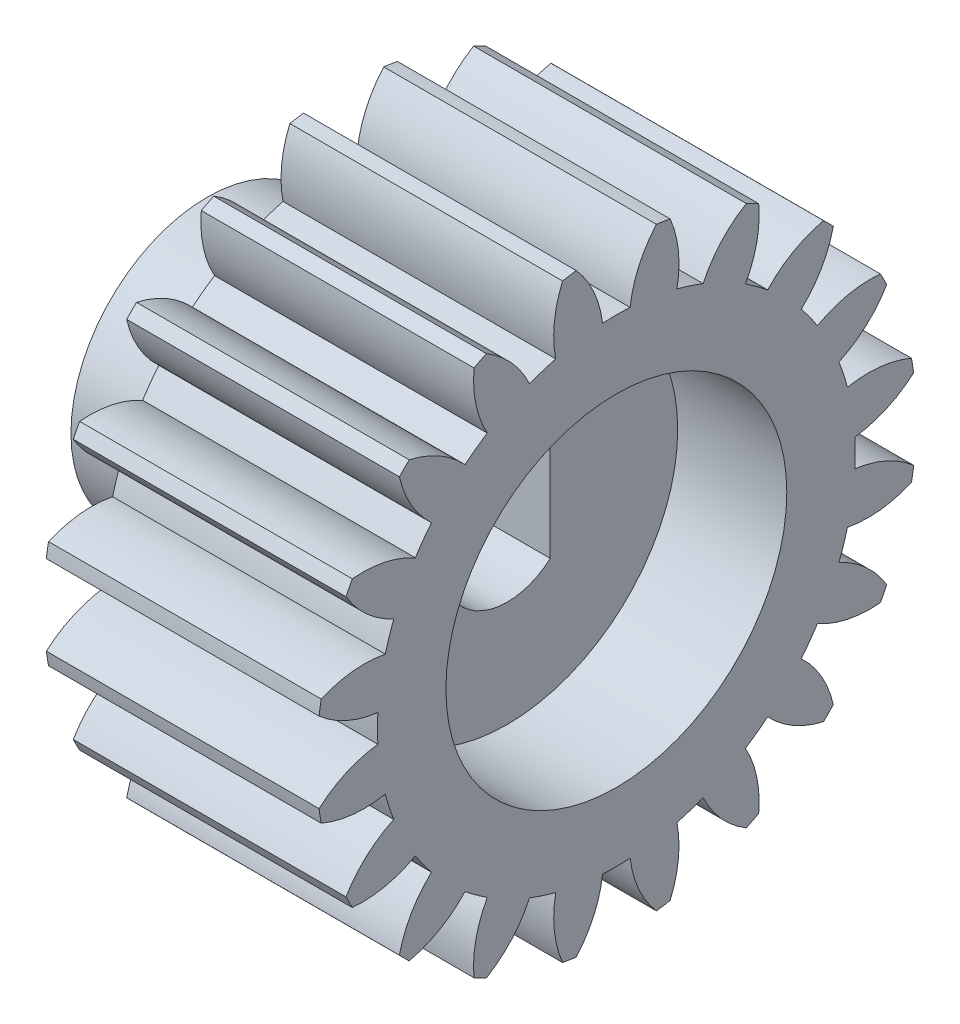
SolidWorks part; units mm, degrees
ref_plane "Plane1" through (0, 0, 0) normal (0, 0, 1) x (1, 0, 0)
ref_plane "Plane2" through (0, 0, 0) normal (0, 1, 0) x (1, 0, 0)
ref_plane "Plane3" through (0, 0, 0) normal (1, 0, 0) x (0, 0, -1)
other "Configuration Table"
sketch "HoldingSke" plane through (0, 0, 0) normal (0, 1, 0) x (1, 0, 0)
  line L0 (0, 0) -> (477.3639, -173.7462)
  line L1 (-15, 0) -> (100, 0) construction
  line L2 (0, 0) -> (-2.1039, 2.3779)
  line L3 (0, 0) -> (-11.863, 4.5341)
  line L4 (0, 0) -> (8.1152, 2.9537)
  line L5 (0, 0) -> (-17.849, -6.6571)
  line L6 (0, 0) -> (-10.5278, -7.1032)
  line L7 (-2.1039, 2.3779) -> (1.9967, 20.9815)
  line L8 (-76.2, 54.61) -> (-69.596, 54.61)
  line L9 (-71.009, 38.7566) -> (-53.1078, 45.2721)
  line L10 (-76.2, 71.12) -> (104.1128, 71.12)
  line L11 (0, 0) -> (-12.7, 0)
  line L12 (-76.2, 101.6) -> (-76.1492, 101.6)
  line L13 (24.9733, 27.94) -> (52.9518, 28.4284)
  line L14 (24.9733, 27.94) -> (25.0241, 27.9398)
  line L15 (24.9733, 27.94) -> (100.4021, 29.52)
  circle A0 centre (0, 0) radius 3.175
  circle A1 centre (0, 0) radius 6.35
  circle A2 centre (0, 0) radius 6.35
  circle A3 centre (0, 0) radius 3.175
  dimension "Num_teeth" = 20
  dimension "H" = 19.05
  dimension "Pitch_radius" = 180.3128
  dimension "Width" = 12.7
  dimension "Thickness" = 12.7
sketch "BasProSke" plane through (0, 0, 0) normal (0, 1, 0) x (1, 0, 0)
  line L0 (-10, 0) -> (60, 0) construction
  line L1 (0, 0) -> (0, 13.97)
  line L2 (0, 0) -> (12.7, 0)
  line L3 (12.7, 0) -> (12.7, 13.97)
  line L4 (12.7, 13.97) -> (0, 13.97)
  dimension "Thickness" = 12.7
  dimension "Diameter" = 27.94
revolve "Base-Revolve" add sketch "BasProSke" angle 360 about L0
sketch "TooCutSke" plane through (0, 0, 0) normal (1, 0, 0) x (0, 0, -1)
  line L1 (0, 0) -> (0, 107) construction
  line L2 (0, 0) -> (-1.0853, 12.6535) construction
  line L3 (0, 0) -> (-3.9633, 25.0231) construction
  line L4 (-1.0853, 12.6535) -> (-1.9816, 12.5116) construction
  arc A0 (0.6405, 11.1067) -> (-0.6405, 11.1067) centre (0, 0) ccw
  arc A1 (1.8856, 13.8678) -> (-1.8856, 13.8678) centre (0, 0) ccw
  circle A2 centre (0, 0) radius 12.7 construction
  circle A3 centre (0, 0) radius 11.9341 construction
  arc A4 (-0.6405, 11.1067) -> (-1.8856, 13.8678) centre (-5.6834, 10.4939) ccw
  arc A5 (1.8856, 13.8678) -> (0.6405, 11.1067) centre (5.6834, 10.4939) ccw
extrude "ToothCut" cut sketch "TooCutSke" along normal through all
fillet "Breaks" [suppressed] radius 0.0254 tangent propagation no
fillet "RootFillets" [suppressed] radius 0.3048
pattern_circular "TeethCuts" count 21 every 18 about axis through (-10, 0, 0) along (1, 0, 0) of "ToothCut"
sketch "HubNeaOneSke" plane through (0, 0, 0) normal (-1, 0, 0) x (0, 0, 1)
  circle A0 centre (0, 0) radius 6.35
  dimension "Diameter" = 12.7
extrude "HubNearOne" add sketch "HubNeaOneSke" along normal blind 6.3502
sketch "HubNeaBotSke" plane through (0, 0, 0) normal (-1, 0, 0) x (0, 0, 1)
  circle A0 centre (0, 0) radius 6.35
  dimension "Diameter" = 12.7
extrude "HubNearBoth" [suppressed] add sketch "HubNeaBotSke" along normal blind 3.1751
ref_plane "FarPln" through (12.7, 0, 0) normal (1, 0, 0) x (0, 0, -1)
sketch "HubFarSke" plane through (12.7, 0, 0) normal (1, 0, 0) x (0, 0, -1)
  circle A0 centre (0, 0) radius 6.35
  dimension "Diameter" = 12.7
extrude "HubFar" [suppressed] add sketch "HubFarSke" along normal blind 3.1751
sketch "BorSke" plane through (0, 0, 0) normal (1, 0, 0) x (0, 0, -1)
  circle A0 centre (0, 0) radius 3.175
  dimension "Diameter" = 6.35
extrude "Bore" cut sketch "BorSke" along normal mid plane 38.1004
sketch "KeySke" plane through (0, 0, 0) normal (1, 0, 0) x (0, 0, -1)
  line L0 (-0.127, 0) -> (-0.127, 3.429)
  line L1 (-0.127, 3.429) -> (0.127, 3.429)
  line L2 (0.127, 3.429) -> (0.127, 0)
  line L3 (0, 0) -> (0, 34) construction
  line L4 (-0.127, 0) -> (0.127, 0)
  dimension "Width" = 0.254
extrude "Keyway" [suppressed] cut sketch "KeySke" along normal mid plane 38.1004
pattern_circular "Keyway2" [suppressed] count 2 every 90 about axis through (-10, 0, 0) along (1, 0, 0) reverse direction yes
ref_axis "Axis1" through (-80.9, 0, 0) along (1, 0, 0)
sketch "Sketch1" plane through (-6.3502, 0, 0) normal (-1, 0, 0) x (0, 0, 1)
  line L0 (-2, 2.2361) -> (-2, -2.2361)
  arc A0 (-2, -2.2361) -> (-2, 2.2361) centre (0, 0) ccw
  circle A1 centre (0, 0) radius 3.175 construction
  circle A2 centre (0, 0) radius 3.175
  dimension "D1" = 6
  dimension "D2" = 2
extrude "Boss-Extrude1" add sketch "Sketch1" against normal up to surface (19.0502 mm away) up to face at (12.7, 0, 3.175)
sketch "Sketch2" plane through (12.7, 0, 0) normal (1, 0, 0) x (0, 0, -1)
  circle A0 centre (0, 0) radius 7.9375
  dimension "D1" = 15.875
extrude "Cut-Extrude1" cut sketch "Sketch2" against normal blind 5.08
equation "' \"Pitch@HoldingSke\" = 4"
equation "' \"Num_teeth@HoldingSke\" = 12"
equation "' \"Ap@HoldingSke\" =  20"
equation "' \"Ap@HoldingSke\" = 20"
equation "' \"Width@HoldingSke\" = 0.5"
equation "' \"Hub_dia@HoldingSke\"= 1"
equation "' \"Hub_dia@HoldingSke\" = 1"
equation "' \"Overall_len@HoldingSke\" = 1.0"
equation "' \"Bore@HoldingSke\" = 0.75"
equation "' \"T_dim@HoldingSke\" = 0.85"
equation "' \"Width@KeySke\" = 0.25"
equation "' \"Show_teeth@HoldingSke\" = 13"
equation "' \"Backlash@HoldingSke\" = 0.009"
equation "' \"Addendum_fac@HoldingSke\" = 1.0"
equation "' \"Dedendum_fac@HoldingSke\" = 1.25"
equation "' \"Dedendum_add@HoldingSke\" = 0.00005"
equation "' \"Clearance_fac@HoldingSke\" = 0.25"
equation "' \"Pitch@HoldingSke\" = 0.5"
equation "' \"Num_teeth@HoldingSke\" = 23"
equation "' \"Show_teeth@HoldingSke\" = 23"
equation "' \"Backlash@HoldingSke\" = 0.0375"
equation "\"Overcut_dia@TooCutSke\" = (\"Num_teeth@HoldingSke\" + 2 * \"Addendum_fac@HoldingSke\") / \"Pitch@HoldingSke\" + 0.002"
equation "\"Pitch_dia@TooCutSke\" = \"Num_teeth@HoldingSke\" / \"Pitch@HoldingSke\""
equation "\"Base_dia@TooCutSke\" = \"Num_teeth@HoldingSke\" / \"Pitch@HoldingSke\" * cos((\"Ap@HoldingSke\"  * 3.14159265 / 180))"
equation "\"Root_dia@TooCutSke\" = (\"Num_teeth@HoldingSke\" + 2) / \"Pitch@HoldingSke\" - 2 * (\"Addendum_fac@HoldingSke\" + \"Dedendum_fac@HoldingSke\") / \"Pitch@HoldingSke\" - \"Dedendum_add@HoldingSke\" * 2"
equation "\"Half_ang@TooCutSke\" = 180 / \"Num_teeth@HoldingSke\""
equation "\"Half_CT@TooCutSke\" = \"Num_teeth@HoldingSke\" / \"Pitch@HoldingSke\" * sin((3.14159265 / 2 / \"Num_teeth@HoldingSke\")) / 2 - 7 * \"Backlash@HoldingSke\" / 4"
equation "\"Flank_rad@TooCutSke\" = \"Num_teeth@HoldingSke\" / \"Pitch@HoldingSke\" / 5"
equation "\"Radius@RootFillets\" = \"Clearance_fac@HoldingSke\" / \"Pitch@HoldingSke\" + \"Dedendum_add@HoldingSke\""
equation "\"Break_rad@Breaks\" = 0.02 / \"Pitch@HoldingSke\""
equation "\"Thickness@HoldingSke\" = \"Width@HoldingSke\""
equation "\"OAL@HoldingSke\" = \"Thickness@HoldingSke\""
equation "\"MHD@HoldingSke\" = (\"Num_teeth@HoldingSke\" + 2) / \"Pitch@HoldingSke\" - 2 * (\"Addendum_fac@HoldingSke\" + \"Dedendum_fac@HoldingSke\")  / \"Pitch@HoldingSke\" - \"Dedendum_add@HoldingSke\" * 2"
equation "\"MBD@HoldingSke\" = (\"Num_teeth@HoldingSke\" + 2) / \"Pitch@HoldingSke\" - 2 * (\"Addendum_fac@HoldingSke\" + \"Dedendum_fac@HoldingSke\")  / \"Pitch@HoldingSke\" - \"Dedendum_add@HoldingSke\" * 2 - 0.002"
equation "\"MHD@HoldingSke\" = ((sgn( \"MHD@HoldingSke\" - \"Hub_dia@HoldingSke\" )-1)*( \"MHD@HoldingSke\" - \"Hub_dia@HoldingSke\" ))/-2+ \"Hub_dia@HoldingSke\""
equation "\"MBD@HoldingSke\" = ((sgn( \"MBD@HoldingSke\" - \"Bore@HoldingSke\" )-1)*( \"MBD@HoldingSke\" - \"Bore@HoldingSke\" ))/-2+ \"Bore@HoldingSke\""
equation "\"OAL@HoldingSke\" = ((sgn( \"OAL@HoldingSke\" - \"Overall_len@HoldingSke\" )+1)*( \"OAL@HoldingSke\" - \"Overall_len@HoldingSke\" ))/2 + \"Overall_len@HoldingSke\" + 0.000002"
equation "\"Num_teeth@TeethCuts\"=int( \"Show_teeth@HoldingSke\" ) + 1"
equation "\"Num_teeth@TeethCuts\" = ((sgn( \"Num_teeth@TeethCuts\" - \"Num_teeth@HoldingSke\" )-1)*( \"Num_teeth@TeethCuts\" - \"Num_teeth@HoldingSke\" ))/-2+ \"Num_teeth@HoldingSke\""
equation "\"Angle@TeethCuts\" = 360.0 / \"Num_teeth@HoldingSke\""
equation "\"Diameter@BasProSke\" = (\"Num_teeth@HoldingSke\" + 2 * \"Addendum_fac@HoldingSke\") / \"Pitch@HoldingSke\""
equation "\"Thickness@BasProSke\"  = \"Thickness@HoldingSke\""
equation "' \"Fillet_rad@BasProSke\" =  \"Thickness@HoldingSke\" * 0.05"
equation "' \"Fillet_rad@BasProSke\" = \"Thickness@HoldingSke\" * 0.05"
equation "\"MHD@HoldingSke\" = ((sgn( \"MHD@HoldingSke\" - \"Root_dia@TooCutSke\" )-1)*( \"MHD@HoldingSke\" - \"Root_dia@TooCutSke\" ))/-2+ \"Root_dia@TooCutSke\""
equation "\"Diameter@HubNeaOneSke\" = \"MHD@HoldingSke\""
equation "\"Length@HubNearOne\" = \"OAL@HoldingSke\" - \"Thickness@BasProSke\""
equation "\"Diameter@HubNeaBotSke\" = \"MHD@HoldingSke\""
equation "\"Length@HubNearBoth\" = ( \"OAL@HoldingSke\" - \"Thickness@BasProSke\" ) / 2.0"
equation "\"Thickness@FarPln\" = \"Thickness@BasProSke\""
equation "\"Diameter@HubFarSke\" = \"MHD@HoldingSke\""
equation "\"Length@HubFar\" = ( \"OAL@HoldingSke\" - \"Thickness@BasProSke\" ) / 2.0"
equation "\"Diameter@BorSke\" = \"MBD@HoldingSke\""
equation "\"D1@Bore\" = \"OAL@HoldingSke\" * 2.0"
equation "\"D1@Keyway\" = \"OAL@HoldingSke\" * 2.0"
equation "\"Offset@KeySke\" = \"T_dim@HoldingSke\" - \"MBD@HoldingSke\" / 2.0"
